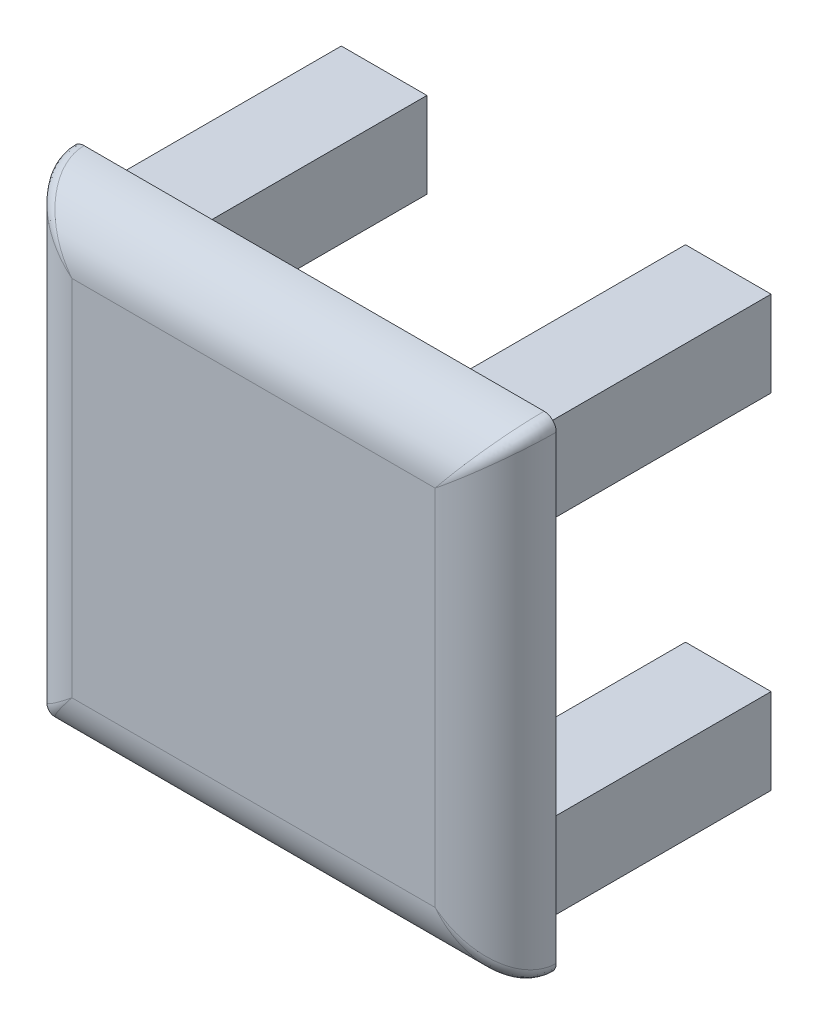
SolidWorks part; units mm, degrees
material "POLIURETAN (11671)"
ref_plane "Płaszczyzna przednia" through (0, 0, 0) normal (0, 0, 1) x (1, 0, 0)
ref_plane "Płaszczyzna górna" through (0, 0, 0) normal (0, 1, 0) x (1, 0, 0)
ref_plane "Płaszczyzna prawa" through (0, 0, 0) normal (1, 0, 0) x (0, 0, -1)
sketch "Szkic1" plane through (0, 0, 0) normal (0, 0, 1) x (1, 0, 0)
  line L0 (4, 20) -> (4, 15.5)
  line L1 (4, 15.5) -> (6.1661, 15.5)
  line L13 (6.1661, 15.5) -> (6.1661, 17.75)
  line L35 (0, 0) -> (40.9069, 40.9069) construction
  line L103 (4, 8.0952) -> (-4, 8.0952)
  line L104 (-10.6789, 10.6789) -> (-10.6789, 17.75)
  line L127 (-10.6789, 17.75) -> (-17.75, 17.75)
  line L128 (-4, 20) -> (-19, 20)
  line L129 (4, 20) -> (19, 20)
  line L131 (10.6789, 10.6789) -> (10.6789, 17.75)
  line L132 (10.6789, 17.75) -> (17.75, 17.75)
  line L134 (-6.1661, 15.5) -> (-6.1661, 17.75)
  line L135 (-4, 15.5) -> (-6.1661, 15.5)
  line L136 (-4, 20) -> (-4, 15.5)
  line L137 (0, 35.4784) -> (0, -28.3735) construction
  line L138 (-42.5787, 0) -> (50.8455, 0) construction
  line L139 (10.6789, 10.6789) -> (17.75, 10.6789)
  line L140 (17.75, 10.6789) -> (17.75, 17.75)
  line L141 (20, 4) -> (20, 19)
  line L142 (15.5, 6.1661) -> (17.75, 6.1661)
  line L143 (15.5, 4) -> (15.5, 6.1661)
  line L144 (20, -4) -> (15.5, -4)
  line L145 (15.5, -4) -> (15.5, -6.1661)
  line L146 (15.5, -6.1661) -> (17.75, -6.1661)
  line L147 (20, -4) -> (20, -19)
  line L148 (17.75, -10.6789) -> (17.75, -17.75)
  line L149 (10.6789, -10.6789) -> (17.75, -10.6789)
  line L150 (8.0952, 4) -> (8.0952, -4)
  line L151 (20, 4) -> (15.5, 4)
  line L152 (-39.6979, 39.6979) -> (27.244, -27.244) construction
  line L153 (4, -20) -> (19, -20)
  line L154 (-20, 4) -> (-20, 19)
  line L155 (-17.75, 10.6789) -> (-17.75, 17.75)
  line L156 (-4, -20) -> (-4, -15.5)
  line L157 (-4, -8.0952) -> (4, -8.0952)
  line L158 (10.6789, -10.6789) -> (10.6789, -17.75)
  line L159 (10.6789, -17.75) -> (17.75, -17.75)
  line L160 (6.1661, -15.5) -> (6.1661, -17.75)
  line L161 (4, -15.5) -> (6.1661, -15.5)
  line L162 (4, -20) -> (4, -15.5)
  line L163 (-4, -15.5) -> (-6.1661, -15.5)
  line L164 (-6.1661, -15.5) -> (-6.1661, -17.75)
  line L165 (-4, -20) -> (-19, -20)
  line L166 (-10.6789, -17.75) -> (-17.75, -17.75)
  line L167 (-10.6789, -10.6789) -> (-10.6789, -17.75)
  line L168 (-20, 4) -> (-15.5, 4)
  line L169 (-15.5, 4) -> (-15.5, 6.1661)
  line L170 (-15.5, 6.1661) -> (-17.75, 6.1661)
  line L171 (-17.75, -10.6789) -> (-17.75, -17.75)
  line L172 (-10.6789, -10.6789) -> (-17.75, -10.6789)
  line L173 (-20, -4) -> (-20, -19)
  line L174 (-10.6789, 10.6789) -> (-17.75, 10.6789)
  line L175 (-8.0952, -4) -> (-8.0952, 4)
  line L176 (-15.5, -6.1661) -> (-17.75, -6.1661)
  line L177 (-15.5, -4) -> (-15.5, -6.1661)
  line L178 (-20, -4) -> (-15.5, -4)
  line L179 (-16.75, 11.6789) -> (-16.75, 16.75)
  line L180 (-11.6789, 16.75) -> (-16.75, 16.75)
  line L181 (-11.6789, 11.6789) -> (-11.6789, 16.75)
  line L182 (-11.6789, 11.6789) -> (-16.75, 11.6789)
  line L183 (-11.6789, -16.75) -> (-16.75, -16.75)
  line L184 (-16.75, -11.6789) -> (-16.75, -16.75)
  line L185 (-11.6789, -11.6789) -> (-16.75, -11.6789)
  line L186 (-11.6789, -11.6789) -> (-11.6789, -16.75)
  line L187 (11.6789, -11.6789) -> (11.6789, -16.75)
  line L188 (11.6789, -16.75) -> (16.75, -16.75)
  line L189 (16.75, -11.6789) -> (16.75, -16.75)
  line L190 (11.6789, -11.6789) -> (16.75, -11.6789)
  line L191 (11.6789, 11.6789) -> (16.75, 11.6789)
  line L192 (16.75, 11.6789) -> (16.75, 16.75)
  line L193 (11.6789, 16.75) -> (16.75, 16.75)
  line L194 (11.6789, 11.6789) -> (11.6789, 16.75)
  arc A57 (6.1661, 17.75) -> (8.4161, 15.5) centre (6.1661, 15.5) cw
  arc A58 (8.4161, 15.5) -> (4, 8.0952) centre (0, 15.5) cw
  arc A59 (-6.1661, 17.75) -> (-8.4161, 15.5) centre (-6.1661, 15.5) ccw
  arc A60 (-8.4161, 15.5) -> (-4, 8.0952) centre (0, 15.5) ccw
  arc A61 (15.5, 8.4161) -> (8.0952, 4) centre (15.5, 0) ccw
  arc A62 (17.75, 6.1661) -> (15.5, 8.4161) centre (15.5, 6.1661) ccw
  arc A63 (15.5, -8.4161) -> (8.0952, -4) centre (15.5, 0) cw
  arc A64 (17.75, -6.1661) -> (15.5, -8.4161) centre (15.5, -6.1661) cw
  arc A65 (6.1661, -17.75) -> (8.4161, -15.5) centre (6.1661, -15.5) ccw
  arc A66 (8.4161, -15.5) -> (4, -8.0952) centre (0, -15.5) ccw
  arc A67 (-6.1661, -17.75) -> (-8.4161, -15.5) centre (-6.1661, -15.5) cw
  arc A68 (-8.4161, -15.5) -> (-4, -8.0952) centre (0, -15.5) cw
  arc A69 (-15.5, 8.4161) -> (-8.0952, 4) centre (-15.5, 0) cw
  arc A70 (-17.75, 6.1661) -> (-15.5, 8.4161) centre (-15.5, 6.1661) cw
  arc A71 (-15.5, -8.4161) -> (-8.0952, -4) centre (-15.5, 0) ccw
  arc A72 (-17.75, -6.1661) -> (-15.5, -8.4161) centre (-15.5, -6.1661) ccw
  arc A73 (-19, -20) -> (-20, -19) centre (-19, -19) cw
  arc A74 (20, -19) -> (19, -20) centre (19, -19) cw
  arc A75 (19, 20) -> (20, 19) centre (19, 19) cw
  arc A76 (-19, 20) -> (-20, 19) centre (-19, 19) ccw
  circle A77 centre (0, 0) radius 4
  circle A78 centre (0, 0) radius 3
  point P9 (4, 17.75)
  point P18 (0, 8.0952)
  point P48 (8.0952, 0)
  point P86 (0, -8.0952)
  point P87 (-8.0952, 0)
  point P91 (-20, -20)
  point P94 (20, -20)
  point P97 (20, 20)
  point P100 (-20, 20)
  dimension "D4" = 8
  dimension "D5" = 1
  dimension "D2" = 10
  dimension "D3" = 40
  dimension "D6" = 8
  dimension "D1" = 4.5
  dimension "D7" = 8.0952
  dimension "D8" = 1
extrude "Dodanie-wyciągnięcie1" add sketch "Szkic1" along normal blind 20 contours L174 L104 L127 L155 L181 L182 L179 L180 | L139 L140 L132 L131 L191 L194 L193 L192 | A77 A78 | L167 L172 L171 L166 L185 L186 L183 L184 | L158 L159 L148 L149 L187 L190 L189 L188 region at (-14.2145, 10.7789, 0) region at (10.7789, 14.2145, 0) region at (17.65, -14.2145, 0) region at (-14.2145, -17.65, 0) region at (-3.8869, 0, 0)
sketch "Szkic2" plane through (0, 0, 20) normal (0, 0, 1) x (1, 0, 0)
  line L1 (-20, -20) -> (20, -20)
  line L2 (-20, -20) -> (-20, 20)
  line L3 (-20, 20) -> (20, 20)
  line L4 (20, -20) -> (20, 20)
  line L5 (-20, -20) -> (20, 20) construction
  line L6 (-20, 20) -> (20, -20) construction
  point P0 (0, 0)
extrude "Dodanie-wyciągnięcie2" add sketch "Szkic2" along normal blind 5
fillet "Zaokrąglenie1" radius 1 4 edges at (20, 20, 22.5) (-20, 20, 22.5) (-20, -20, 22.5) (20, -20, 22.5)
fillet "Zaokrąglenie2" radius 5 8 edges at (19.7071, -19.7071, 25) (0, -20, 25) (-19.7071, -19.7071, 25) (-20, 0, 25) (-19.7071, 19.7071, 25) (0, 20, 25) (19.7071, 19.7071, 25) (20, 0, 25)
